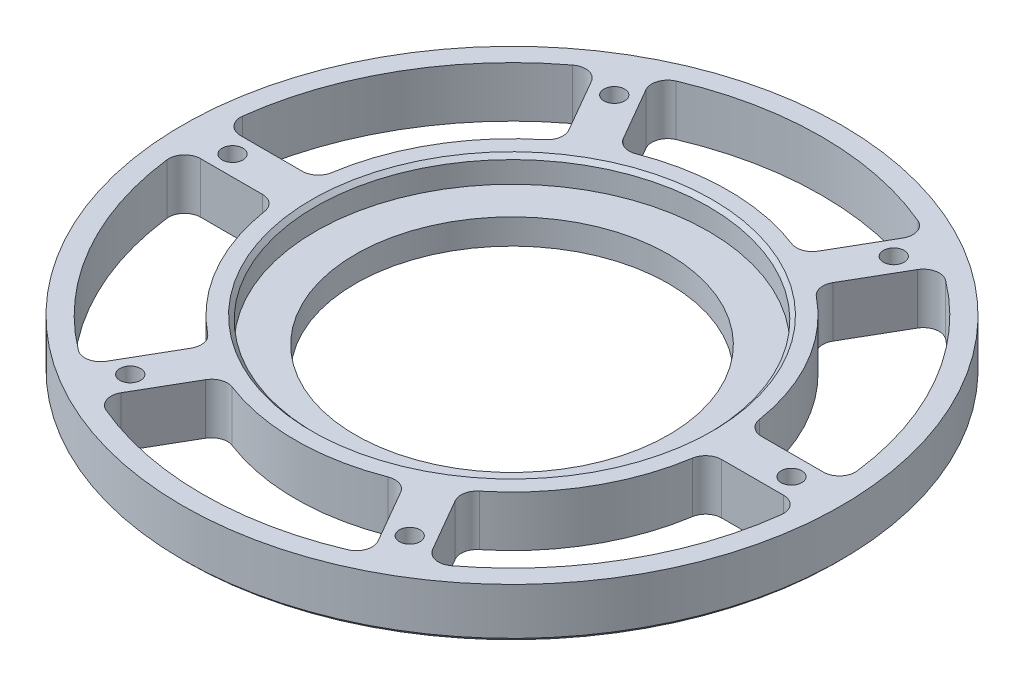
SolidWorks part; units mm, degrees
material "6061-T6 (SS)"
ref_plane "Front Plane" through (0, 0, 0) normal (0, 0, 1) x (1, 0, 0)
ref_plane "Top Plane" through (0, 0, 0) normal (0, 1, 0) x (1, 0, 0)
ref_plane "Right Plane" through (0, 0, 0) normal (1, 0, 0) x (0, 0, -1)
sketch "Sketch2" plane through (0, 0, 0) normal (1, 0, 0) x (0, 0, -1)
  line L0 (-39.2125, 0) -> (-82.55, 0)
  line L1 (-82.55, 0) -> (-82.55, 12.7)
  line L2 (-82.55, 12.7) -> (-49.2125, 12.7)
  line L3 (-49.2125, 12.7) -> (-49.2125, 6.35)
  line L4 (-49.2125, 6.35) -> (-39.2125, 6.35)
  line L5 (-39.2125, 6.35) -> (-39.2125, 0)
  dimension "D1" = 82.55
  dimension "D2" = 12.7
  dimension "D4" = 49.2125
  dimension "D5" = 10
  dimension "D3" = 6.35
ref_axis "Axis1" through (0, -0.9525, 0) along (0, 1, 0)
revolve "Revolve1" add sketch "Sketch2" angle 360 about axis through (0, -0.9525, 0) along (0, 1, 0)
hole_wizard "#6 (0.204) Diameter Hole1" positions "Sketch6" profile "Sketch7" hole size "#6" standard "ANSI Inch" end condition through all
sketch "Sketch6" plane through (0, 12.7, 0) normal (0, 1, 0) x (1, 0, 0)
  line L0 (0, 0) -> (-69.8201, 120.932) construction
  line L2 (0, 0) -> (0, 109.0908) construction
  point P0 (-35, 60.6218)
  dimension "D1" = 30
  dimension "D2" = 70
sketch "Sketch7" plane through (-35, 12.7, -60.6218) normal (1, 0, 0) x (0, 0, 1)
  line L0 (0, 0) -> (0, 12.7)
  line L1 (0, 12.7) -> (2.5908, 12.7)
  line L2 (2.5908, 12.7) -> (2.5908, 0)
  line L5 (2.5908, 0) -> (0, 0)
  line L11 (0, -6.35) -> (0, 107.95) construction
  dimension "Thru Hole Dia." = 5.1816
  dimension "Thru Hole Depth" = 12.7
pattern_circular "CirPattern3" count 6 over 360 about axis through (0, -0.9525, 0) along (0, 1, 0) of "#6 (0.204) Diameter Hole1"
sketch "Sketch8" plane through (0, 12.7, 0) normal (0, 1, 0) x (1, 0, 0)
  line L0 (-34.3642, 69.5205) -> (-22.6606, 49.2493)
  line L1 (34.3642, 69.5205) -> (22.6606, 49.2493)
  line L2 (0, 0) -> (-35, 60.6218) construction
  line L4 (0, 0) -> (0, 93.9995) construction
  arc A0 (-22.6606, 49.2493) -> (22.6606, 49.2493) centre (0, 0) cw
  arc A1 (-34.3642, 69.5205) -> (34.3642, 69.5205) centre (0, 0) cw
  circle A2 centre (0, 0) radius 49.2125 construction
  circle A3 centre (0, 0) radius 82.55 construction
  dimension "D1" = 5
  dimension "D2" = 5
  dimension "D3" = 5
extrude "Cut-Extrude1" cut sketch "Sketch8" against normal through all
fillet "Fillet1" radius 4 4 edges at (34.3642, 6.35, -69.5205) (22.6606, 6.35, -49.2493) (-34.3642, 6.35, -69.5205) (-22.6606, 6.35, -49.2493)
pattern_circular "CirPattern4" count 6 over 360 about axis through (0, -0.9525, 0) along (0, 1, 0) of "Cut-Extrude1", "Fillet1"
chamfer "Chamfer1" distance 1 angle 45 1 edges at (0, 12.7, -49.2125)
chamfer "Chamfer2" distance 1 angle 45 1 edges at (0, 0, -82.55)
equation "\"TubeDiameter\" = 6.500in"
equation "\"D1@Sketch2\"=\"TubeDiameter\"/2"
